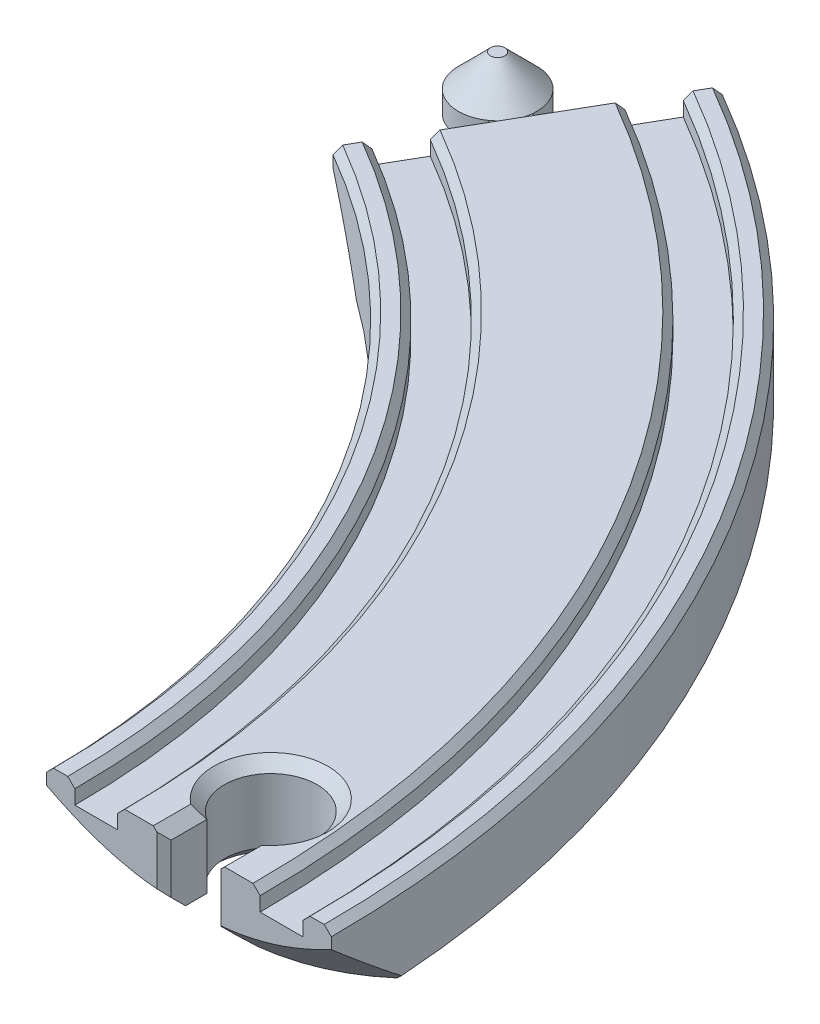
SolidWorks part; units mm, degrees
ref_plane "Front Plane" through (0, 0, 0) normal (0, 0, 1) x (1, 0, 0)
ref_plane "Top Plane" through (0, 0, 0) normal (0, 1, 0) x (1, 0, 0)
ref_plane "Right Plane" through (0, 0, 0) normal (1, 0, 0) x (0, 0, -1)
sketch "Sketch2" plane through (0, 0, 0) normal (0, 0, 1) x (1, 0, 0)
  line L0 (-20, 0) -> (20, 0)
  line L1 (20, 0) -> (20, 12)
  line L2 (20, 12) -> (16, 12)
  line L3 (16, 12) -> (16, 9)
  line L4 (16, 9) -> (10, 9)
  line L5 (10, 9) -> (10, 12)
  line L6 (10, 12) -> (-10, 12)
  line L7 (-10, 12) -> (-10, 9)
  line L8 (-10, 9) -> (-16, 9)
  line L9 (-16, 9) -> (-16, 12)
  line L10 (-16, 12) -> (-20, 12)
  line L11 (-20, 12) -> (-20, 0)
  line L12 (-129.9038, 0) -> (-129.9038, 12)
  point P4 (0, 0)
  dimension "D1" = 40
  dimension "D2" = 12
  dimension "D3" = 3
  dimension "D4" = 4
  dimension "D5" = 6
  dimension "D6" = 129.9038
revolve "Revolve1" add sketch "Sketch2" angle 60 about L12 region at (0, 5.6351, 0)
sketch "Sketch3" plane through (0, 12, 0) normal (0, 1, 0) x (1, 0, 0)
  line L0 (10, 0) -> (-10, 0) construction
  line L2 (-3.5, 0) -> (3.5, 0)
  line L3 (-3.5, 0) -> (-3.5, 11.5)
  line L4 (-3.5, 11.5) -> (3.5, 11.5)
  line L5 (3.5, 0) -> (3.5, 11.5)
  line L6 (-3.5, 0) -> (3.5, 11.5) construction
  line L7 (-3.5, 11.5) -> (3.5, 0) construction
  circle A0 centre (0, 11.5) radius 6.5
  point P4 (0, 5.75)
  point P10 (0, 0)
  line M6 (-10, 0) -> (10, 0)
  dimension "D1" = 13
  dimension "D2" = 11.5
  dimension "D3" = 7
extrude "Cut-Extrude1" cut sketch "Sketch3" against normal through all contours L5 A0 L3 L4 | L3 A0 L5 L4 | A0 L3 L5 M6 region at (0, 12, -2.6732) region at (0, 12, -12.9919) region at (0, 12, -8.4074)
sketch "Sketch4" plane through (0, 12, 0) normal (0, 1, 0) x (1, 0, 0)
  line L0 (-63.8269, 114.4486) -> (-66.0769, 110.5514)
  line L1 (-63.8269, 114.4486) -> (-73.7862, 120.1986)
  line L2 (-66.0769, 110.5514) -> (-76.0362, 116.3014)
  line L3 (-73.7862, 120.1986) -> (-76.0362, 116.3014)
  line L4 (-59.9519, 121.1603) -> (-69.9519, 103.8397) construction
  circle A0 centre (-74.9112, 118.25) radius 5.5
  point P9 (-64.9519, 112.5)
  line M6 (-59.9519, 121.1603) -> (-69.9519, 103.8397)
  dimension "D1" = 11
  dimension "D2" = 4.5
  dimension "D3" = 11.5
extrude "Boss-Extrude1" add sketch "Sketch4" against normal up to surface (12 mm away) contours L1 A0 L2 L3 | L2 A0 L1 L3 region at (-72.5962, 12, -116.9134) region at (-75.6952, 12, -118.7026) up to face at (-12.4699, 0, -33.3033)
extrude "Boss-Extrude2" add sketch "Sketch4<3>" against normal blind 7.5 contours A0 L2 L1 M6 region at (-67.6196, 12, -114.0402)
sketch "Sketch4<3>" plane through (0, 12, 0) normal (0, 1, 0) x (1, 0, 0) same geometry as "Sketch4"
extrude "Cut-Extrude2" cut sketch "Sketch4<5>" against normal blind 4.5 contours A0 L2 L1 M6 region at (-67.6196, 12, -114.0402)
sketch "Sketch4<5>" plane through (0, 12, 0) normal (0, 1, 0) x (1, 0, 0) same geometry as "Sketch4"
chamfer "Chamfer2" distance 4.5 angle 45 1 edges at (-80.4112, 12, -118.25)
chamfer "Chamfer5" distance 3 distance2 4.5 1 edges at (-74.9112, 0, -123.75) first distance on face at (-74.9112, 0, -123.75)
chamfer "Chamfer3" distance 1.5 angle 45 6 edges at (0, 0, -18) (0, 12, -18) (3.5, 0, -3.0114) (-3.5, 0, -3.0114) (3.5, 12, -3.0114) (-3.5, 12, -3.0114)
sketch "Sketch17" plane through (31.351, 0, -54.3014) normal (-0.5, 0, 0.866) x (0.866, 0, 0.5)
  line L0 (-118.9813, 10.9813) -> (-118.9813, 0)
  line L1 (-118.9813, 0) -> (-108, 0)
  line L2 (-108, 0) -> (-118.9813, 10.9813)
  line L4 (-83, -1.2652) -> (-83, 10.9813) construction
  dimension "D1" = 25
revolve "Cut-Revolve1" cut sketch "Sketch17" angle 90 about L4
ref_plane "Plane1" through (32.476, 0, -56.25) normal (-0.5, 0, 0.866) x (0.866, 0, 0.5)
mirror "Mirror1" about plane through (32.476, 0, -56.25) normal (-0.5, 0, 0.866) of "Cut-Revolve1"
chamfer "Chamfer4" distance 4.5 angle 45 1 edges at (-64.9519, 0, -112.5)
ref_plane "Plane2" through (-32.476, 0, -56.25) normal (-0.5, 0, -0.866) x (-0.866, 0, 0.5)
mirror "Mirror4" about plane through (-32.476, 0, -56.25) normal (-0.5, 0, -0.866) of "Cut-Revolve1", "Mirror1"
chamfer "Chamfer1" distance 1 angle 45 10 edges at (-0.0833, 12, -74.9519) (-3.5474, 12, -72.9519) (-8.7436, 12, -69.9519) (-26.0641, 12, -59.9519) (-31.2602, 12, -56.9519) (-34.7243, 12, -54.9519) (-0.0833, 0, -74.9519) (-34.7243, 0, -54.9519) (3.5, 7.5132, 0) (-3.5, 7.5132, 0)
